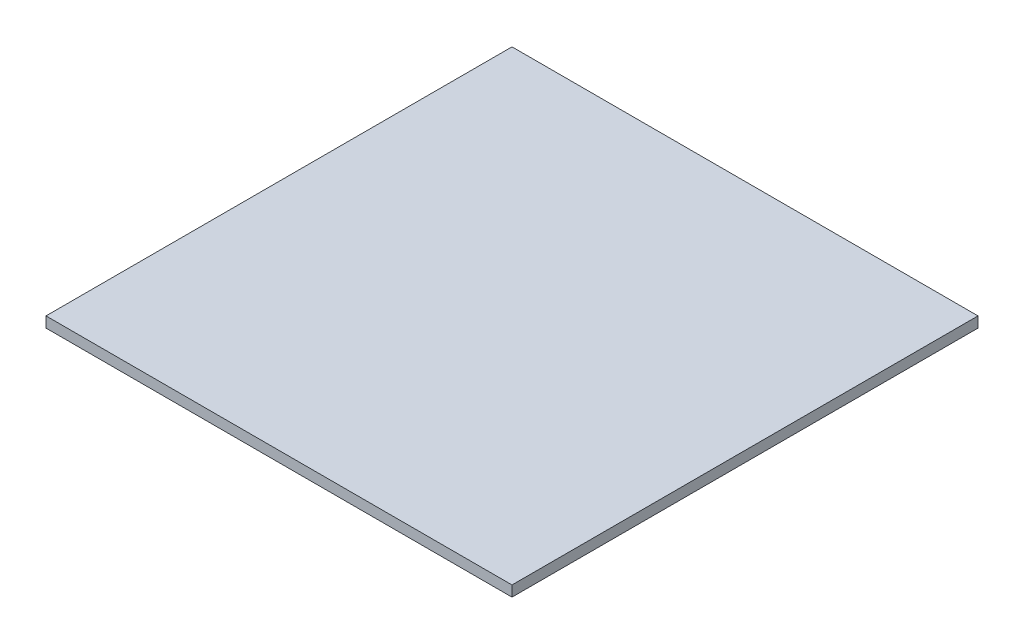
SolidWorks part; units mm, degrees
ref_plane "Front Plane" through (0, 0, 0) normal (0, 0, 1) x (1, 0, 0)
ref_plane "Top Plane" through (0, 0, 0) normal (0, 1, 0) x (1, 0, 0)
ref_plane "Right Plane" through (0, 0, 0) normal (1, 0, 0) x (0, 0, -1)
sketch "Sketch1" plane through (0, 0, 0) normal (0, 1, 0) x (1, 0, 0)
  line L0 (-50.6753, 48.6342) -> (-48.1353, 51.1742)
  line L1 (-48.1353, -50.4258) -> (48.3847, -50.4258)
  line L2 (-50.6753, -47.8858) -> (-50.6753, 48.6342)
  line L3 (-48.1353, 51.1742) -> (48.3847, 51.1742)
  line L4 (50.9247, -47.8858) -> (50.9247, 48.6342)
  line L5 (-50.6753, -50.4258) -> (50.9247, 51.1742) construction
  line L6 (-50.6753, 51.1742) -> (50.9247, -50.4258) construction
  line L7 (48.3847, 51.1742) -> (50.9247, 48.6342)
  line L8 (48.3847, -50.4258) -> (50.9247, -47.8858)
  line L9 (-50.6753, -47.8858) -> (-48.1353, -50.4258)
  line L10 (-41.1503, 41.6492) -> (0.1247, 41.6492)
  line L11 (41.3997, -40.9008) -> (-41.1503, -40.9008) construction
  line L12 (41.3997, -40.9008) -> (41.3997, 41.6492) construction
  line L13 (41.3997, 41.6492) -> (-41.1503, 41.6492) construction
  line L14 (-41.1503, -40.9008) -> (-41.1503, 41.6492) construction
  line L15 (41.3997, -40.9008) -> (-41.1503, 41.6492) construction
  line L16 (41.3997, 41.6492) -> (-41.1503, -40.9008) construction
  line L17 (41.3997, -40.9008) -> (0.1247, -40.9008)
  line L18 (-34.8003, -34.5508) -> (35.0497, -34.5508)
  line L19 (-34.8003, -34.5508) -> (-34.8003, 35.2992)
  line L20 (-34.8003, 35.2992) -> (35.0497, 35.2992)
  line L21 (35.0497, -34.5508) -> (35.0497, 35.2992)
  line L22 (-34.8003, -34.5508) -> (35.0497, 35.2992) construction
  line L23 (-34.8003, 35.2992) -> (35.0497, -34.5508) construction
  circle A0 centre (-41.1503, 41.6492) radius 3.2639
  circle A1 centre (0.1247, 41.6492) radius 3.2639
  circle A2 centre (41.3997, 41.6492) radius 3.2639
  circle A3 centre (41.3997, 0.3742) radius 3.2639
  circle A4 centre (41.3997, -40.9008) radius 3.2639
  circle A5 centre (0.1247, -40.9008) radius 3.2639
  circle A6 centre (-41.1503, -40.9008) radius 3.2639
  circle A7 centre (-41.1503, 0.3742) radius 3.2639
  circle A8 centre (-20.5128, 41.6492) radius 4.7625
  circle A9 centre (20.7622, -40.9008) radius 4.7625
  point P0 (0.1247, 0.3742)
  point P13 (0.1247, 0.3742)
  point P34 (0.1247, 0.3742)
  dimension "D13" = 6.5278
  dimension "D14" = 9.525
  dimension "D1" = 101.6
  dimension "D2" = 101.6
  dimension "D3" = 2.54
  dimension "D4" = 2.54
  dimension "D5" = 2.54
  dimension "D6" = 2.54
  dimension "D7" = 2.54
  dimension "D8" = 2.54
  dimension "D9" = 2.54
  dimension "D10" = 2.54
  dimension "D11" = 82.55
  dimension "D12" = 82.55
  dimension "D15" = 69.85
  dimension "D16" = 69.85
extrude "Boss-Extrude1" add sketch "Sketch1" along normal blind 1.5875 contours L18 L21 L20 L19 region at (0.1247, 0, -0.3742)
